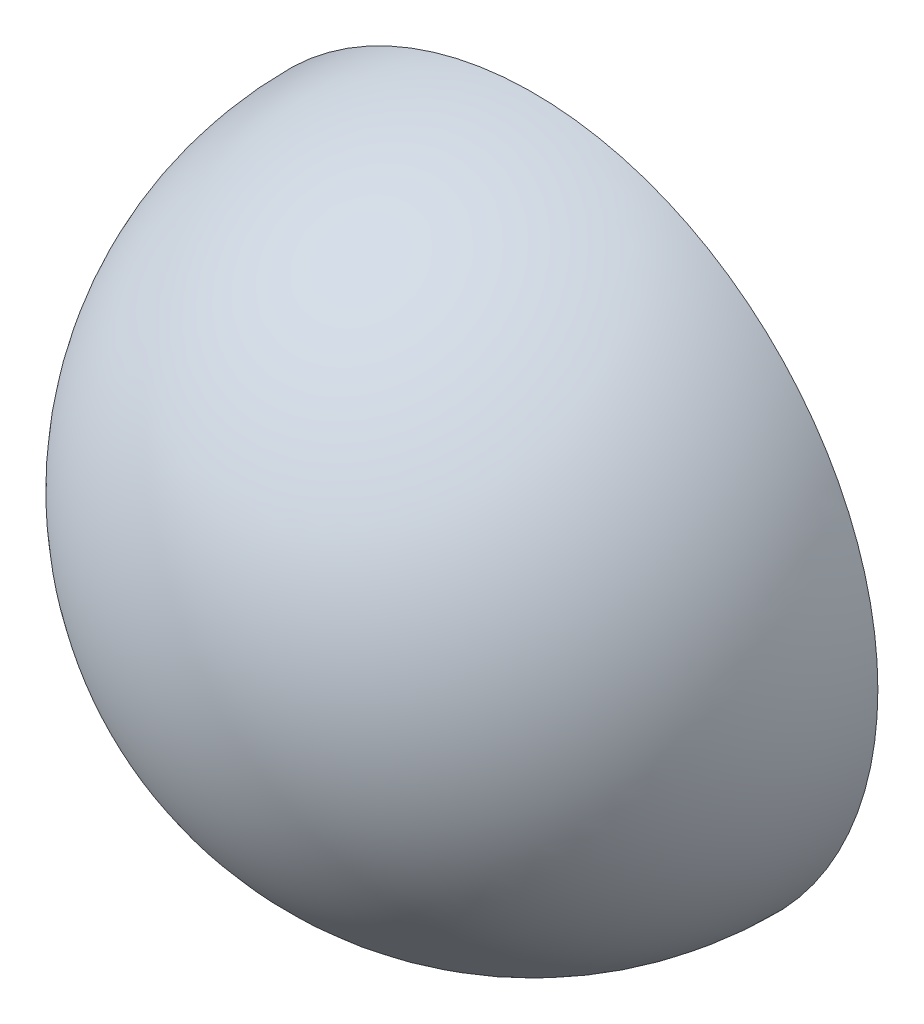
SolidWorks part; units mm, degrees
ref_plane "正面" through (0, 0, 0) normal (0, 0, 1) x (1, 0, 0)
ref_plane "平面" through (0, 0, 0) normal (0, 1, 0) x (1, 0, 0)
ref_plane "右側面" through (0, 0, 0) normal (1, 0, 0) x (0, 0, -1)
sketch "ｽｹｯﾁ1" plane through (0, 0, 0) normal (0, 0, 1) x (1, 0, 0)
  line L0 (-16.15, 0) -> (-14.65, 0)
  line L1 (14.65, 0) -> (16.15, 0)
  line L2 (14.65, 0) -> (-14.65, 0) construction
  arc A0 (14.65, 0) -> (-14.65, 0) centre (0, 0) cw
  arc A1 (-16.15, 0) -> (16.15, 0) centre (0, 0) ccw
  dimension "D2" = 14.65
  dimension "D1" = 1.5
revolve "回転1" add sketch "ｽｹｯﾁ1" angle 180 about L2
